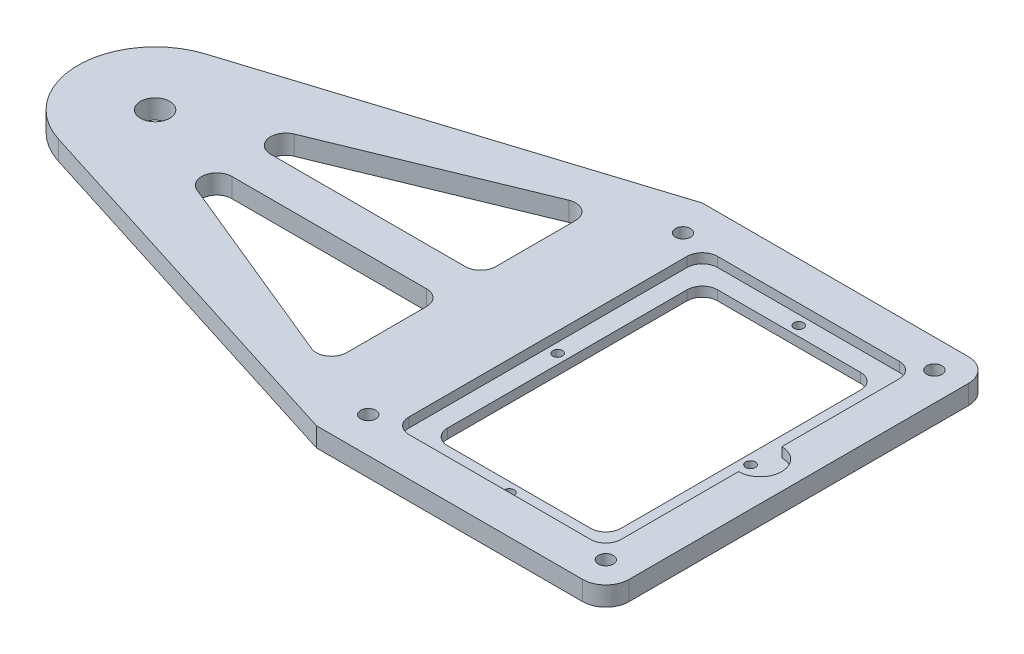
SolidWorks part; units mm, degrees
material "UHMW"
ref_plane "Front Plane" through (0, 0, 0) normal (0, 0, 1) x (1, 0, 0)
ref_plane "Top Plane" through (0, 0, 0) normal (0, 1, 0) x (1, 0, 0)
ref_plane "Right Plane" through (0, 0, 0) normal (1, 0, 0) x (0, 0, -1)
sketch "Sketch1" plane through (0, 0, 0) normal (0, 1, 0) x (1, 0, 0)
  line L0 (-47.625, 0) -> (47.625, 0) construction
  line L1 (-47.625, -63.5) -> (47.625, -63.5)
  line L2 (-47.625, -63.5) -> (-47.625, 63.5)
  line L3 (-47.625, 63.5) -> (47.625, 63.5)
  line L4 (47.625, -63.5) -> (47.625, 63.5)
  line L5 (-47.625, -63.5) -> (47.625, 63.5) construction
  line L6 (-47.625, 63.5) -> (47.625, -63.5) construction
  point P0 (0, 0)
  dimension "D1" = 95.25
  dimension "D2" = 127
  dimension "D3" = 63.5
extrude "Boss-Extrude1" add sketch "Sketch1" along normal blind 6.35
sketch "Sketch4" plane through (0, 6.35, 0) normal (0, 1, 0) x (1, 0, 0)
  line L1 (-47.625, 63.5) -> (-171.916, 24.2193)
  line L5 (-47.625, 63.5) -> (-47.625, -63.5) construction
  line L9 (-47.625, -63.5) -> (-171.916, -24.2193)
  line L10 (-47.625, 63.5) -> (-47.625, -63.5)
  arc A0 (-171.916, 24.2193) -> (-171.916, -24.2193) centre (-164.2618, 0) ccw
  circle A1 centre (-48.9458, 0) radius 2.5 construction
  dimension "D1" = 50.8
  dimension "D2" = 115.316
extrude "Boss-Extrude3" add sketch "Sketch4" against normal blind 6.35
sketch "Sketch5" plane through (0, 6.35, 0) normal (0, 1, 0) x (1, 0, 0)
  circle A0 centre (-164.2618, 0) radius 4.826
  circle A1 centre (-8.6868, 0) radius 4.826
  arc A2 (-171.916, 24.2193) -> (-171.916, -24.2193) centre (-164.2618, 0) ccw construction
  arc A3 (-171.916, 24.2193) -> (-171.916, -24.2193) centre (-164.2618, 0) ccw
  dimension "D1" = 9.652
  dimension "D2" = 155.575
extrude "Cut-Extrude1" cut sketch "Sketch5" against normal through all contours A0 | A1 region at (-164.2618, 6.35, 0) region at (-8.6868, 6.35, 0)
sketch "Sketch6" plane through (0, 6.35, 0) normal (0, 1, 0) x (1, 0, 0)
  line L0 (-63.5, 6.35) -> (-63.5, -6.35) construction
  line L1 (-63.5, 45.1637) -> (-157.9118, 6.35)
  line L2 (-157.9118, 6.35) -> (-63.5, 6.35)
  line L3 (-63.5, 6.35) -> (-63.5, 45.1637)
  line L4 (-63.5, -6.35) -> (-63.5, -45.1637)
  line L5 (-63.5, -45.1637) -> (-157.9118, -6.35)
  line L6 (-157.9118, -6.35) -> (-63.5, -6.35)
  line L7 (0, 0) -> (-63.5, 0) construction
  line L8 (-47.625, 63.5) -> (-171.916, 24.2193) construction
  line L9 (-189.6618, 78.2466) -> (-189.6618, -78.2466) construction
  arc A1 (-171.916, 24.2193) -> (-171.916, -24.2193) centre (-164.2618, 0) ccw construction
  point P10 (-189.6618, 0)
  dimension "D1" = 12.7
  dimension "D2" = 31.75
  dimension "D3" = 12.7
  dimension "D4" = 63.5
extrude "Cut-Extrude2" cut sketch "Sketch6" against normal through all
fillet "Fillet9" radius 5 6 edges at (-157.9118, 3.175, 6.35) (-63.5, 3.175, 6.35) (-63.5, 3.175, 45.1637) (-63.5, 3.175, -6.35) (-157.9118, 3.175, -6.35) (-63.5, 3.175, -45.1637)
sketch "Sketch7" plane through (0, 6.35, 0) normal (0, 1, 0) x (1, 0, 0)
  circle A0 centre (-8.6868, 0) radius 5.4538
extrude "Boss-Extrude4" add sketch "Sketch7" against normal blind 6.35
sketch "Sketch8" plane through (0, 6.35, 0) normal (0, 1, 0) x (1, 0, 0)
  line L4 (-47.625, -63.5) -> (47.625, -63.5) construction
  line L5 (-34.925, 50.8) -> (-34.925, -50.8)
  line L7 (-47.625, 63.5) -> (-47.625, -63.5) construction
  line L8 (-171.916, -24.2193) -> (-47.625, -63.5) construction
  line L10 (47.625, 50.8) -> (-47.625, 50.8)
  line L11 (34.925, 50.8) -> (-34.925, 50.8)
  line L13 (34.925, -63.5) -> (34.925, 63.5)
  line L14 (34.925, -50.8) -> (34.925, 50.8)
  line L15 (-34.925, 63.5) -> (-34.925, -63.5) construction
  line L16 (-47.625, -50.8) -> (47.625, -50.8)
  line L17 (-34.925, -50.8) -> (34.925, -50.8)
  dimension "D1" = 12.7
  dimension "D2" = 12.7
  dimension "D3" = 12.7
  dimension "D4" = 12.7
extrude "Cut-Extrude3" cut sketch "Sketch8" against normal blind 3.175
sketch "Sketch9" plane through (0, 3.175, 0) normal (0, 1, 0) x (1, 0, 0)
  line L14 (-28.575, -44.45) -> (28.575, -44.45)
  line L15 (28.575, -44.45) -> (28.575, 44.45)
  line L16 (-28.575, 44.45) -> (-28.575, -44.45)
  line L17 (28.575, 44.45) -> (-28.575, 44.45)
  line L18 (-28.575, -44.45) -> (28.575, -44.45)
  line L19 (28.575, -44.45) -> (28.575, 44.45)
  line L20 (-28.575, 44.45) -> (-28.575, -44.45)
  line L21 (28.575, 44.45) -> (-28.575, 44.45)
  dimension "D1" = 6.35
extrude "Cut-Extrude4" cut sketch "Sketch9" against normal through all
sketch "Sketch11" plane through (0, 3.175, 0) normal (0, 1, 0) x (1, 0, 0)
  line L0 (0, 50.8) -> (0, -50.8) construction
  line L1 (34.925, 50.8) -> (-34.925, 50.8) construction
  line L2 (-34.925, -50.8) -> (34.925, -50.8) construction
  line L3 (-34.925, 0) -> (34.925, 0) construction
  line L4 (-34.925, 50.8) -> (-34.925, -50.8) construction
  line L5 (34.925, -50.8) -> (34.925, 50.8) construction
  line L6 (-34.925, 50.8) -> (-34.925, -50.8) construction
  line L7 (-28.575, 44.45) -> (-28.575, -44.45) construction
  line L8 (34.925, 50.8) -> (-34.925, 50.8) construction
  circle A0 centre (-31.75, 0) radius 1.5875
  circle A1 centre (31.75, 0) radius 1.5875
  circle A2 centre (0, 47.625) radius 1.5875
  circle A3 centre (0, -47.625) radius 1.5875
  dimension "D1" = 3.175
  dimension "D4" = 3.175
  dimension "D2" = 3.175
  dimension "D3" = 3.175
  dimension "D5" = 3.175
extrude "Cut-Extrude6" cut sketch "Sketch11" against normal through all
sketch "Sketch12" plane through (0, 6.35, 0) normal (0, 1, 0) x (1, 0, 0)
  line L0 (34.925, -50.8) -> (34.925, 50.8) construction
  line L1 (34.925, 7.112) -> (34.925, 50.8) construction
  line L2 (34.925, -7.112) -> (34.925, -50.8) construction
  line L3 (34.925, 0) -> (-34.925, 0) construction
  line L4 (-34.925, 50.8) -> (-34.925, -50.8) construction
  line L5 (34.925, -50.8) -> (34.925, 50.8) construction
  line L6 (34.925, 7.112) -> (34.925, -7.112)
  arc A0 (34.925, 7.112) -> (34.925, -7.112) centre (34.925, 0) cw
  dimension "D1" = 7.112
extrude "Cut-Extrude7" cut sketch "Sketch12" against normal blind 3.175
fillet "Fillet10" radius 5 4 edges at (-34.925, 4.7625, 50.8) (34.925, 4.7625, 50.8) (34.925, 4.7625, -50.8) (-34.925, 4.7625, -50.8)
fillet "Fillet11" radius 5 4 edges at (-28.575, 1.5875, -44.45) (28.575, 1.5875, -44.45) (28.575, 1.5875, 44.45) (-28.575, 1.5875, 44.45)
fillet "Fillet12" radius 7.62 2 edges at (47.625, 3.175, -63.5) (47.625, 3.175, 63.5)
sketch "Sketch13" plane through (0, 6.35, 0) normal (0, 1, 0) x (1, 0, 0)
  circle A0 centre (-42.2861, 51.8111) radius 2.4892
  circle A1 centre (-42.2861, -51.8111) radius 2.4892
  circle A2 centre (38.2023, -54.0773) radius 2.4892
  circle A3 centre (38.2023, 54.0773) radius 2.4892
  dimension "D1" = 4.9784
extrude "Cut-Extrude8" cut sketch "Sketch13" against normal through all
